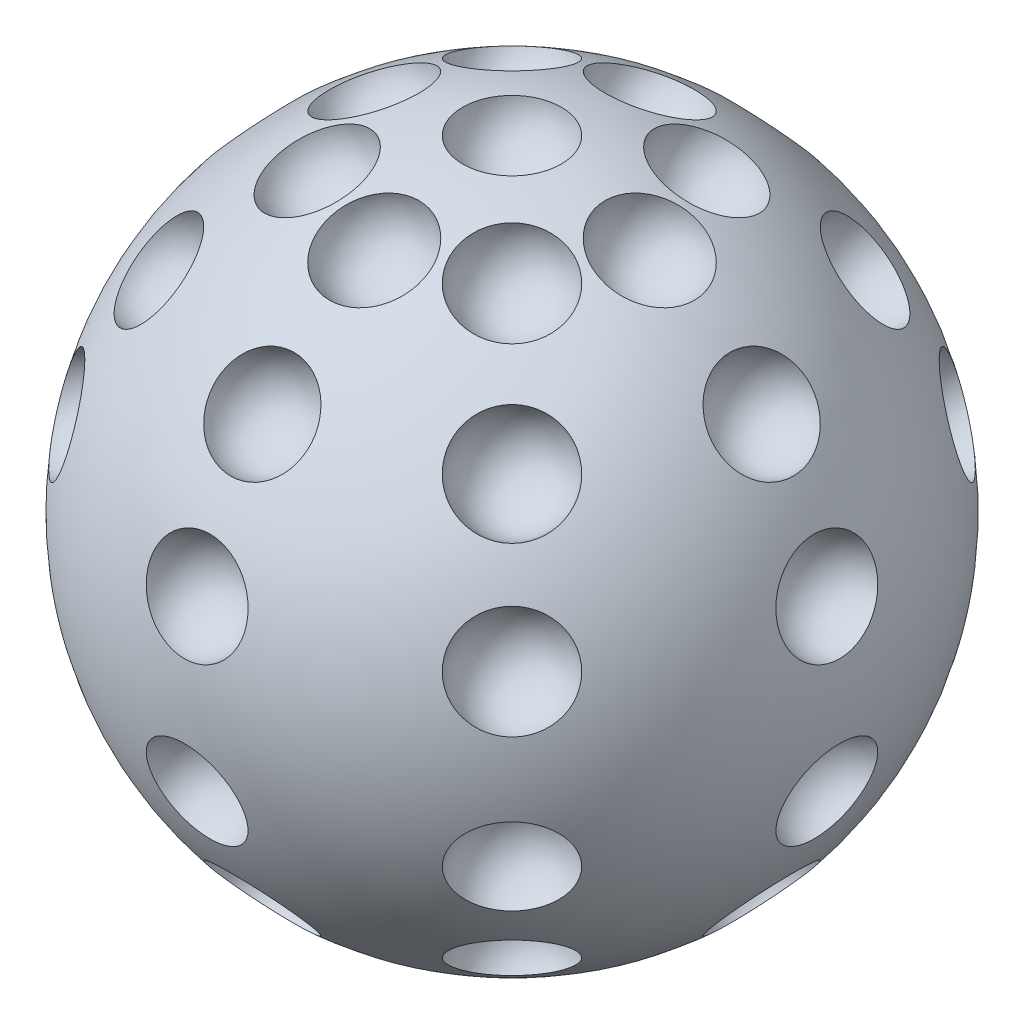
SolidWorks part; units mm, degrees
note: '?' marks a value the reader was unsure of.
ref_plane "Front Plane" through (0, 0, 0) normal (0, 0, 1) x (1, 0, 0)
ref_plane "Top Plane" through (0, 0, 0) normal (0, 1, 0) x (1, 0, 0)
ref_plane "Right Plane" through (0, 0, 0) normal (1, 0, 0) x (0, 0, -1)
sketch "Sketch1" plane through (0, 0, 0) normal (0, 0, 1) x (1, 0, 0)
  line L0 (0, 0) -> (20, 0)
  line L1 (0, 0) -> (0, 20)
  arc A0 (0, 20) -> (20, 0) centre (0, 0) cw
  dimension "D1" = 20
revolve "Revolve1" add sketch "Sketch1" angle 360 about L1
sketch "Sketch2" plane through (0, 0, 0) normal (1, 0, 0) x (0, 0, -1)
  line L0 (0, 17) -> (0, 20)
  arc A0 (20, 0) -> (-20, 0) centre (0, 0) ccw construction
  arc A1 (0, 17) -> (-2.9916, 19.775) centre (0, 20) cw
  arc A2 (0, 20) -> (-2.9916, 19.775) centre (0, 0) ccw
  dimension "D1" = 3
revolve "Cut-Revolve1" cut sketch "Sketch2" angle 360 about L0
ref_axis "Axis1" through (0, 0, -11) along (0, 0, 1)?
ref_axis "Axis2" through (-11, 0, 0) along (1, 0, 0)?
pattern_circular "CirPattern1" count 4 every 25 about axis through (0, 0, 0) along (1, 0, 0) of "Cut-Revolve1"
pattern_circular "CirPattern2" count 8 over 360 of "CirPattern1"
mirror "Mirror1" about plane through (0, 0, 0) normal (0, -1, 0) of bodies 104
